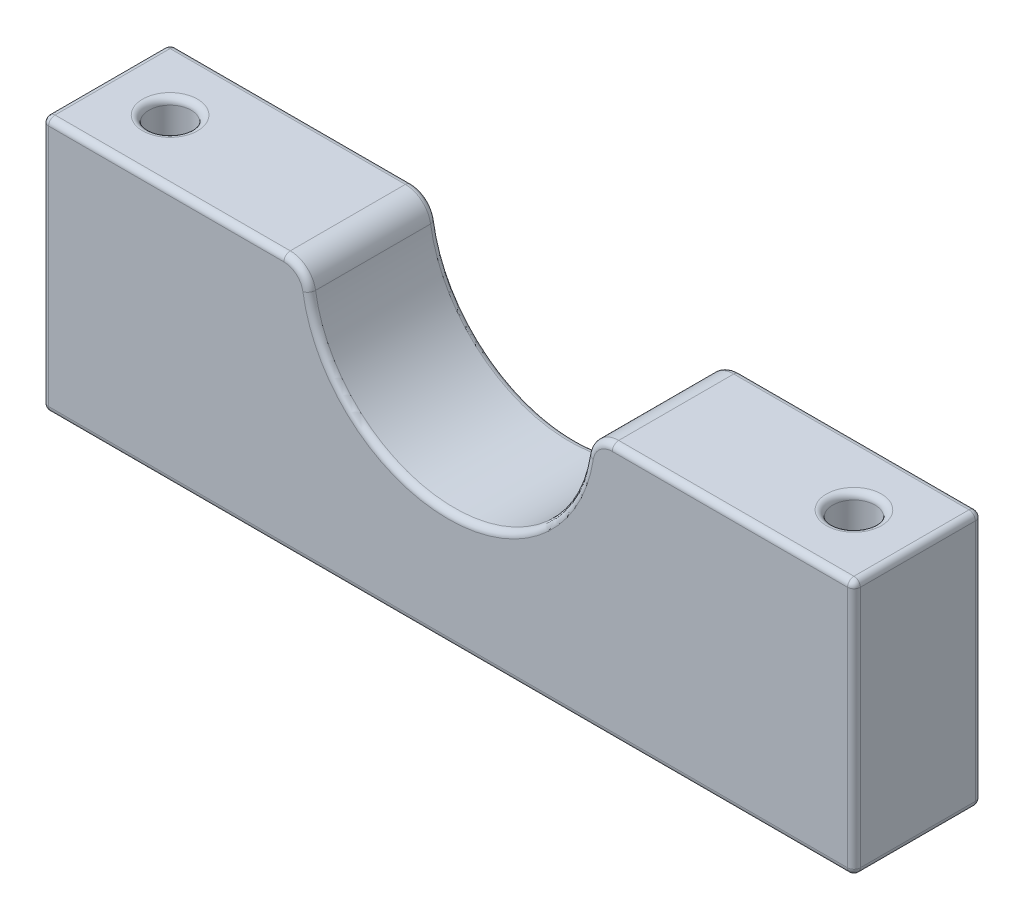
SolidWorks part; units mm, degrees
ref_plane "Спереди" through (0, 0, 0) normal (0, 0, 1) x (1, 0, 0)
ref_plane "Сверху" through (0, 0, 0) normal (0, 1, 0) x (1, 0, 0)
ref_plane "Справа" through (0, 0, 0) normal (1, 0, 0) x (0, 0, -1)
sketch "Эскиз1" plane through (0, 0, 0) normal (0, 0, 1) x (1, 0, 0)
  line L0 (0, 24.9844) -> (0, -42.4233) construction
  line L1 (11, 0) -> (31.75, 0)
  line L2 (-31.75, 0) -> (-11, 0)
  line L3 (-31.75, 0) -> (-31.75, -20)
  line L4 (-31.75, -20) -> (31.75, -20)
  line L5 (31.75, 0) -> (31.75, -20)
  line L6 (-31.75, 0) -> (31.75, -20) construction
  line L7 (-31.75, -20) -> (31.75, 0) construction
  arc A0 (-11, 0) -> (11, 0) centre (0, 0) ccw
  point P5 (0, -10)
  dimension "D1" = 22
  dimension "D2" = 63.5
  dimension "D3" = 20
extrude "Бобышка-Вытянуть1" add sketch "Эскиз1" along normal blind 10
sketch "Эскиз2" plane through (0, -20, 0) normal (0, -1, 0) x (1, 0, 0)
  line L0 (-31.75, 5) -> (31.75, 5) construction
  line L1 (-31.75, 10) -> (-31.75, 0) construction
  line L2 (31.75, 10) -> (31.75, 0) construction
  line L3 (-26.75, 10) -> (-26.75, 0) construction
  line L4 (-31.75, 10) -> (31.75, 10) construction
  line L5 (-31.75, 0) -> (31.75, 0) construction
  line L6 (26.75, 10) -> (26.75, 0) construction
  dimension "D1" = 5
  dimension "D2" = 5
hole_wizard "Отверстие обработанное метчиком M4x0.71" positions "Эскиз4" profile "Эскиз3" tap size "M4x0.7" standard "Ansi Metric" end condition through all
sketch "Эскиз4" plane through (0, -20, 0) normal (0, -1, 0) x (-1, 0, 0)
  line L0 (26.75, -10) -> (26.75, 0) construction
  line L1 (-26.75, -10) -> (-26.75, 0) construction
  point P0 (26.75, -5)
  point P4 (-26.75, -5)
sketch "Эскиз3" plane through (-26.75, -20, 5) normal (1, 0, 0) x (0, 0, -1)
  line L0 (0, 0) -> (0, 20)
  line L1 (0, 20) -> (1.65, 20)
  line L2 (1.65, 20) -> (1.65, 0)
  line L5 (1.65, 0) -> (0, 0)
  line L11 (0, -6.35) -> (0, 107.95) construction
  dimension "Диаметр проходного сверла" = 3.3
  dimension "Глубина проходного сверла" = 20
cosmetic thread "Отверстие резьбы1" parameters "D2"=4
cosmetic thread "Отверстие резьбы2" parameters "D2"=4
fillet "Скругление2" radius 2 2 edges at (11, 0, 5) (-11, 0, 5)
fillet "Скругление1" radius 0.5 24 edges at (31.75, 0, 5) (26.75, 0, 3.35) (-31.75, 0, 5) (-26.75, 0, 3.35) (-31.75, -20, 5) (31.75, -20, 5) (26.75, -20, 3.35) (-26.75, -20, 3.35) (-22.2976, 0, 0) (-31.75, -10, 0) (0, -20, 0) (31.75, -10, 0) (22.2976, 0, 0) (0, -11, 0) (22.2976, 0, 10) (31.75, -10, 10) (0, -20, 10) (-31.75, -10, 10) (-22.2976, 0, 10) (0, -11, 10) (-11.5443, -0.4809, 0) (11.5443, -0.4809, 0) (-11.5443, -0.4809, 10) (11.5443, -0.4809, 10)
